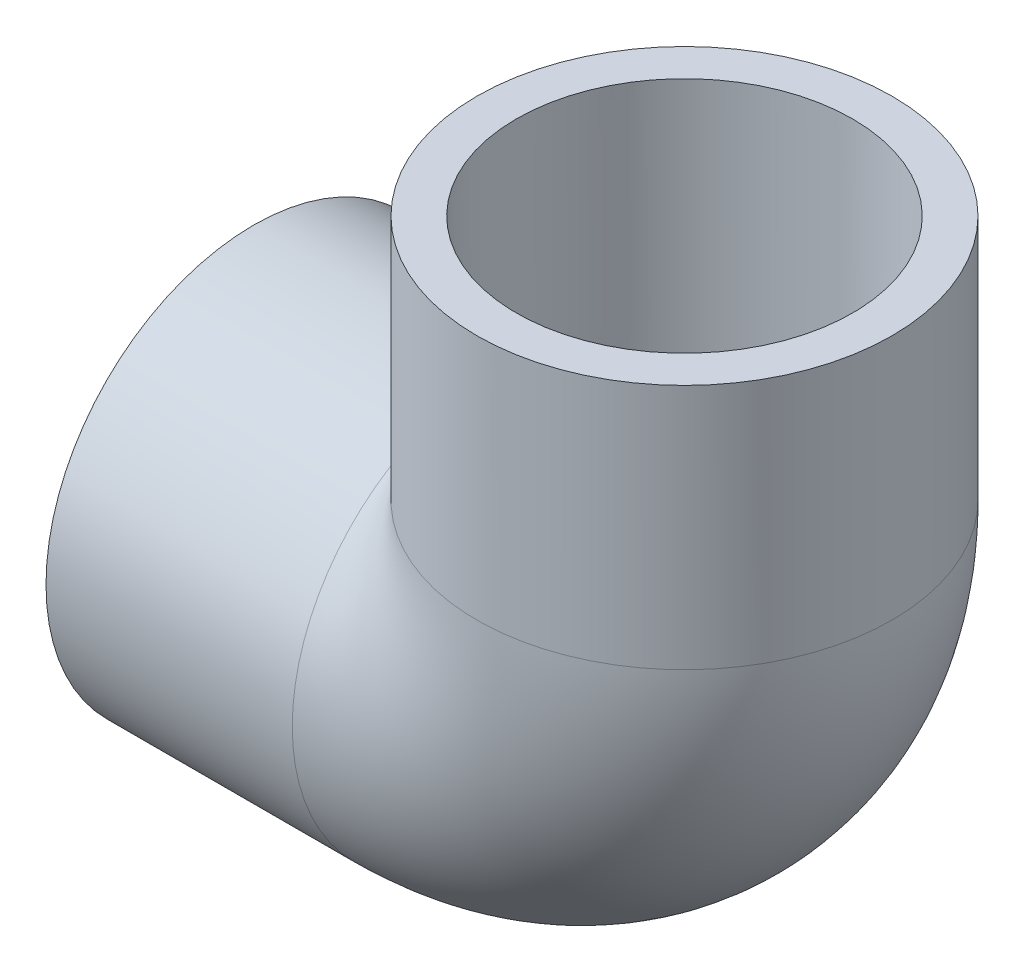
SolidWorks part; units mm, degrees
material "ABS"
ref_plane "Front Plane" through (0, 0, 0) normal (0, 0, 1) x (1, 0, 0)
ref_plane "Top Plane" through (0, 0, 0) normal (0, 1, 0) x (1, 0, 0)
ref_plane "Right Plane" through (0, 0, 0) normal (1, 0, 0) x (0, 0, -1)
sketch "Sketch0" plane through (0, 0, 0) normal (0, 0, 1) x (1, 0, 0)
  line L0 (-62.23, 0) -> (0, 0) construction
  line L1 (0, 0) -> (0, 62.23) construction
  line L2 (-26.67, 0) -> (0, 0) construction
  line L3 (0, 0) -> (0, 26.67) construction
  line L4 (-62.23, 29.972) -> (-62.23, -29.972) construction
  line L5 (-26.67, 24.0538) -> (-62.23, 24.2824) construction
  line L6 (-26.67, 24.0538) -> (-26.67, -24.0538) construction
  line L7 (-26.67, -24.0538) -> (-62.23, -24.2824) construction
  line L8 (-62.23, 24.2824) -> (-62.23, -24.2824) construction
  line L9 (-29.972, 62.23) -> (29.972, 62.23) construction
  line L10 (-24.2824, 62.23) -> (24.2824, 62.23) construction
  line L11 (24.2824, 62.23) -> (24.0538, 26.67) construction
  line L12 (24.0538, 26.67) -> (-24.0538, 26.67) construction
  line L13 (-24.0538, 26.67) -> (-24.2824, 62.23) construction
  line L14 (-26.67, 19.05) -> (-26.67, -19.05) construction
  line L18 (-19.05, 26.67) -> (19.05, 26.67) construction
  dimension "H" = 62.23
  dimension "G" = 26.67
  dimension "M" = 59.944
  dimension "OD A" = 48.5648
  dimension "OD B" = 48.1076
  dimension "ID" = 38.1
sketch "Sketch1" plane through (0, 0, 0) normal (0, 0, 1) x (1, 0, 0)
  line L0 (-62.23, 0) -> (0, 0) construction
  line L1 (-62.23, 0) -> (0, 0) construction
  line L3 (-62.23, -29.972) -> (-26.67, -29.972)
  line L4 (-62.23, -29.972) -> (-62.23, -24.2824)
  line L5 (-62.23, -24.2824) -> (-26.67, -24.0538)
  line L6 (-26.67, -29.972) -> (-26.67, -24.0538)
revolve "Revolve1" add sketch "Sketch1" angle 360 about L1
sketch "Sketch2" plane through (0, 0, 0) normal (0, 0, 1) x (1, 0, 0)
  line L0 (24.2824, 62.23) -> (24.0538, 26.67)
  line L1 (24.0538, 26.67) -> (29.972, 26.67)
  line L2 (29.972, 26.67) -> (29.972, 62.23)
  line L3 (29.972, 62.23) -> (24.2824, 62.23)
  line L4 (0, 0) -> (0, 62.23) construction
  line L5 (0, 0) -> (0, 62.23) construction
revolve "Revolve2" add sketch "Sketch2" angle 360 about L5
sketch "Sketch3" plane through (-26.67, 0, 0) normal (1, 0, 0) x (0, 0, -1)
  circle A0 centre (0, 0) radius 19.05
  circle A1 centre (0, 0) radius 29.972
sketch "Sketch4" plane through (0, 0, 0) normal (0, 0, 1) x (1, 0, 0)
  line L0 (-62.23, 0) -> (0, 0) construction
  line L1 (0, 0) -> (0, 62.23) construction
  line L2 (-62.23, 0) -> (-26.67, 0) construction
  line L3 (0, 26.67) -> (0, 62.23) construction
  arc A0 (-26.67, 0) -> (0, 26.67) centre (-26.67, 26.67) ccw
sweep "Sweep1" add profiles "Sketch3" path "Sketch4"
other "CPoint1" parameters "Diameter"=38.1, "StubLength"=28.575
ref_axis "Axis1" through (-36.67, 0, 0) along (1, 0, 0)
other "CPoint2" parameters "Diameter"=38.1, "StubLength"=57.15
ref_axis "Axis2" through (0, 36.67, 0) along (0, -1, 0)
other "RPoint1"
